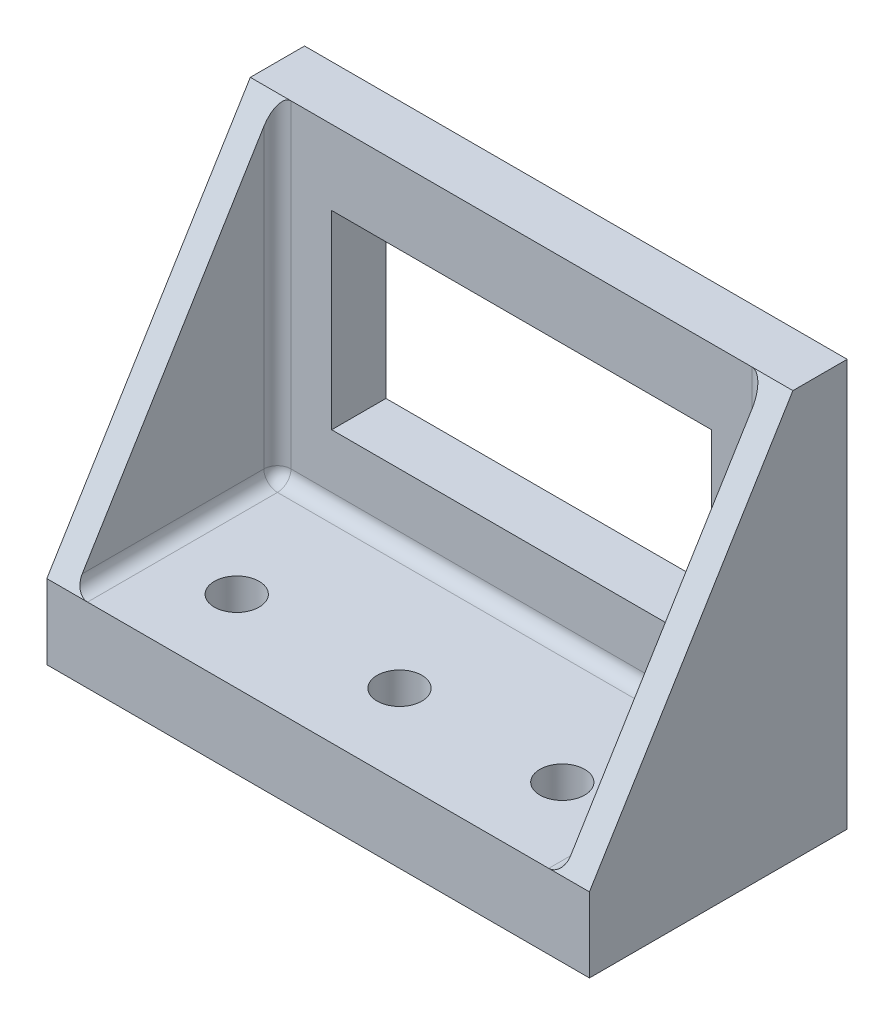
SolidWorks part; units mm, degrees
ref_plane "Front" through (0, 0, 0) normal (0, 0, 1) x (1, 0, 0)
ref_plane "Top" through (0, 0, 0) normal (0, 1, 0) x (1, 0, 0)
ref_plane "Right" through (0, 0, 0) normal (1, 0, 0) x (0, 0, -1)
sketch "Sketch1" plane through (0, 0, 0) normal (0, 0, 1) x (1, 0, 0)
  line L1 (-20.2222, 10.7222) -> (19.7778, 10.7222)
  line L2 (-20.2222, 10.7222) -> (-20.2222, -19.2778)
  line L3 (-20.2222, -19.2778) -> (19.7778, -19.2778)
  line L4 (19.7778, 10.7222) -> (19.7778, -19.2778)
  dimension "D1" = 40
  dimension "D2" = 30
extrude "Boss-Extrude1" add sketch "Sketch1" along normal blind 4
sketch "Sketch4" plane through (0, 0, 4) normal (0, 0, 1) x (1, 0, 0)
  line L0 (-20.2222, 10.7222) -> (-20.2222, -19.2778) construction
  line L2 (-14.2222, -8.7778) -> (-14.2222, 5.2222)
  line L3 (-14.2222, 5.2222) -> (13.7778, 5.2222)
  line L4 (13.7778, -8.7778) -> (13.7778, 5.2222)
  line L7 (-14.2222, -8.7778) -> (13.7778, -8.7778)
  line L9 (19.7778, 10.7222) -> (-20.2222, 10.7222) construction
  dimension "D1" = 28
  dimension "D2" = 14
  dimension "D3" = 6
  dimension "D4" = 5.5
extrude "Cut-Extrude1" cut sketch "Sketch4" against normal blind 5.5
sketch "Sketch5" plane through (0, 0, 4) normal (0, 0, 1) x (1, 0, 0)
  line L0 (19.7778, -19.2778) -> (19.7778, 10.7222) construction
  line L1 (-20.2222, -19.2778) -> (19.7778, -19.2778)
  line L2 (-20.2222, -19.2778) -> (-20.2222, -13.7778)
  line L3 (-20.2222, -13.7778) -> (19.7778, -13.7778)
  line L4 (19.7778, -19.2778) -> (19.7778, -13.7778)
  dimension "D1" = 5.5
extrude "Boss-Extrude2" add sketch "Sketch5" along normal blind 15
sketch "Sketch6" plane through (0, -19.2778, 0) normal (0, -1, 0) x (1, 0, 0)
  line L1 (-20.2222, 19) -> (-20.2222, 0) construction
  circle A0 centre (-12.2222, 13) radius 1.65
  circle A1 centre (-0.2222, 13) radius 1.65
  circle A2 centre (11.7778, 13) radius 1.65
  dimension "D1" = 3.3
  dimension "D2" = 8
  dimension "D3" = 3
extrude "Cut-Extrude3" cut sketch "Sketch6" against normal blind 15
sketch "Sketch8" plane through (-20.2222, 0, 0) normal (-1, 0, 0) x (0, 0, 1)
  line L0 (4, 10.7222) -> (19, -13.7778)
rib "Rib1" sketch "Sketch8" sketch "Sketch8" thickness 2 extrusion direction parallel to sketch draft on no parameters "D1"=2
sketch "Sketch11" plane through (19.7778, 0, 0) normal (1, 0, 0) x (0, 0, -1)
  line L0 (-19, -13.7778) -> (-4, 10.7222)
rib "Rib14" sketch "Sketch11" sketch "Sketch11" thickness 2 extrusion direction parallel to sketch draft on no parameters "D1"=2
fillet "Fillet1" radius 1 5 edges at (17.7778, -13.7778, 11.5) (-18.2222, -13.7778, 11.5) (-0.2222, -13.7778, 4) (17.7778, -1.5278, 4) (-18.2222, -1.5278, 4)
